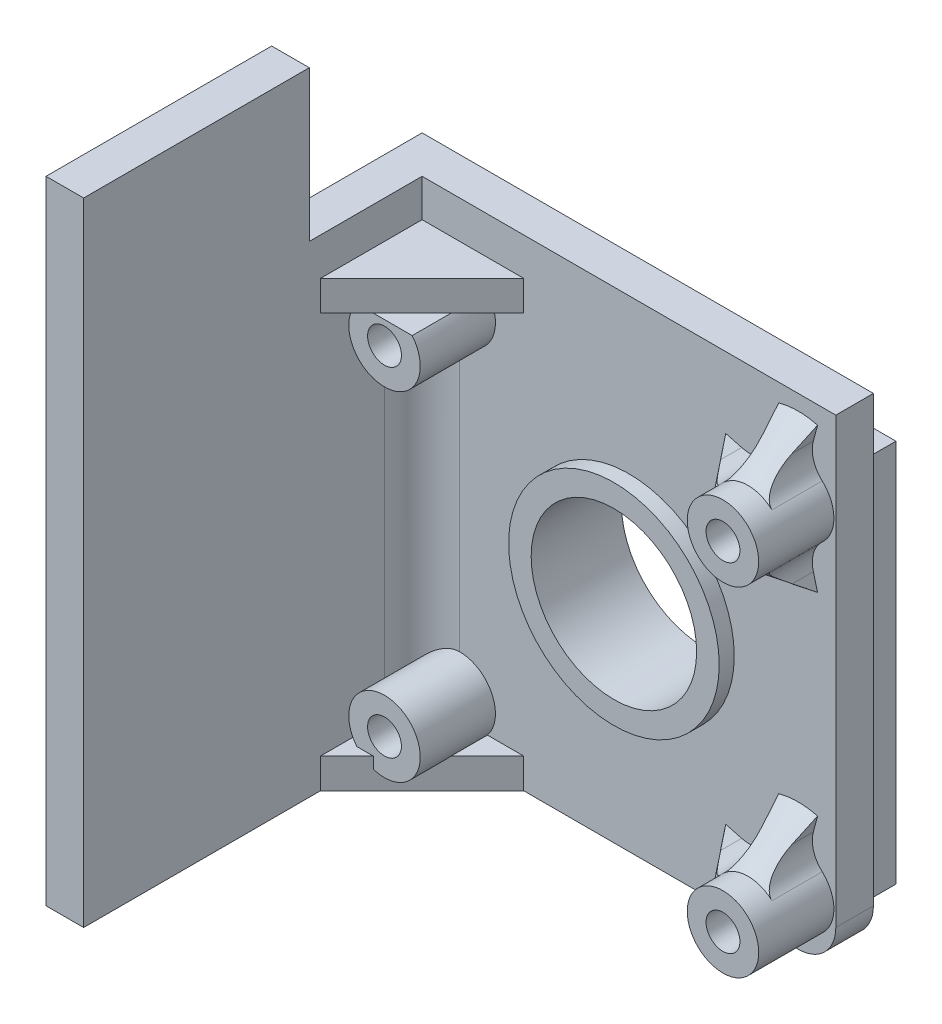
SolidWorks part; units mm, degrees
note: '?' marks a value the reader was unsure of.
ref_plane "Front Plane" through (0, 0, 0) normal (0, 0, 1) x (1, 0, 0)
ref_plane "Top Plane" through (0, 0, 0) normal (0, 1, 0) x (1, 0, 0)
ref_plane "Right Plane" through (0, 0, 0) normal (1, 0, 0) x (0, 0, -1)
sketch "Sketch2" plane through (0, 0, 0) normal (0, 0, 1) x (1, 0, 0)
  line L0 (0, 0) -> (45, 45) construction
  line L1 (0, 0) -> (45, 0)
  line L2 (0, 0) -> (0, 45)
  line L3 (0, 45) -> (45, 45)
  line L4 (45, 0) -> (45, 45)
  line L6 (-5, 52) -> (50, 52)
  line L7 (-5, 52) -> (-5, -7)
  line L8 (-5, -7) -> (50, -7)
  line L9 (50, 52) -> (50, -7)
  line L10 (-5, 52) -> (50, -7) construction
  line L11 (-5, -7) -> (50, 52) construction
  circle A0 centre (0, 45) radius 1.6
  circle A1 centre (45, 45) radius 1.6
  circle A2 centre (45, 0) radius 1.6
  circle A3 centre (0, 0) radius 1.6
  circle A4 centre (22.5, 22.5) radius 11
  point P9 (22.5, 22.5)
  dimension "D3" = 3.2
  dimension "D6" = 22
  dimension "D1" = 45
  dimension "D2" = 45
  dimension "D4" = 5
  dimension "D5" = 7
extrude "Boss-Extrude1" add sketch "Sketch2" along normal blind 5 contours L9 L6 L7 L8 A3 L2 A0 L3 A1 L4 A2 L1 | A3 L1 A2 L4 A1 L3 A0 L2
sketch "Sketch4" plane through (0, 0, 0) normal (0, 0, -1) x (-1, 0, 0)
  line L0 (5, 52) -> (-50, 52) construction
  line L1 (5, -7) -> (10, -7)
  line L2 (5, -7) -> (5, 52)
  line L3 (5, 52) -> (10, 52)
  line L4 (10, -7) -> (10, 52)
  dimension "D1" = 5
extrude "Boss-Extrude2" add sketch "Sketch4" against normal blind 50
sketch "Sketch5" plane through (0, 52, 0) normal (0, 1, 0) x (1, 0, 0)
  line L0 (-5, -5) -> (8.5128, -5)
  line L1 (-5, -5) -> (50, -5) construction
  line L2 (8.5128, -5) -> (-5, -18.5128)
  line L3 (-5, -50) -> (-5, -5) construction
  line L4 (-5, -18.5128) -> (-5, -5)
  point P2 (0, 0)
  point P5 (-10, -9.0838)
  point P7 (0, 0)
  point P10 (8.5128, -5)
extrude "Boss-Extrude3" add sketch "Sketch5" against normal blind 4
ref_plane "Plane1" through (0, 22.5, 0) normal (0, 1, 0) x (1, 0, 0)
fillet "Fillet2" radius 5 1 edges at (50, -7, 2.5)
sketch "Sketch7" plane through (0, 52, 0) normal (0, 1, 0) x (1, 0, 0)
  line L0 (-5, -50) -> (-10, -50) construction
  line L1 (-5, -50) -> (-10, -50)
  line L2 (-5, -50) -> (-5, 0)
  line L3 (-5, 0) -> (-10, 0)
  line L4 (-10, -50) -> (-10, 0)
  line L6 (-10, 0) -> (50, 0) construction
  line L7 (-10, -50) -> (-10, 0) construction
  point P12 (0, 0)
extrude "Boss-Extrude4" add sketch "Sketch7" along normal blind 5
sketch "Sketch8" plane through (-10, 0, 0) normal (-1, 0, 0) x (0, 0, 1)
  line L1 (5, 52) -> (0, 52)
  line L2 (5, 52) -> (5, 57)
  line L3 (5, 57) -> (0, 57)
  line L4 (0, 52) -> (0, 57)
extrude "Boss-Extrude5" add sketch "Sketch8" along normal up to surface (60 mm away)
sketch "Sketch10" plane through (0, 0, 5) normal (0, 0, 1) x (1, 0, 0)
  line L6 (-5, 48) -> (-5, -7)
  line L7 (-5, 48) -> (-5, -7)
  line L8 (-5, -7) -> (45, -7)
  line L9 (50, -2) -> (50, 57)
  line L10 (50, 57) -> (-5, 57)
  line L11 (-5, 57) -> (-5, 52)
  line L12 (-5, 52) -> (8.5128, 52)
  line L15 (8.5128, 52) -> (8.5128, 48)
  line L16 (-5, -7) -> (45, -7)
  line L17 (50, -2) -> (50, 57)
  line L18 (50, 57) -> (-5, 57)
  line L20 (-5, 52) -> (8.5128, 52)
  line L24 (8.5128, 52) -> (8.5128, 48)
  line L25 (8.5128, 48) -> (-5, 48)
  line L26 (8.5128, 48) -> (-5, 48)
  line L27 (-5, 57) -> (-5, 52)
  circle A0 centre (0, 45) radius 4.75
  arc A1 (45, -7) -> (50, -2) centre (45, -2) ccw
  arc A2 (45, -7) -> (50, -2) centre (45, -2) ccw
  circle A3 centre (45, 45) radius 4.75
  circle A4 centre (45, 0) radius 4.75
  circle A5 centre (0, 0) radius 4.75
  circle A6 centre (45, 45) radius 2.25
  circle A7 centre (0, 45) radius 2.25
  circle A8 centre (0, 0) radius 2.25
  circle A9 centre (45, 0) radius 2.25
  dimension "D2" = 9.5
  dimension "D3" = 4.5
  dimension "D1" = 0
extrude "Boss-Extrude6" add sketch "Sketch10" along normal blind 10
ref_axis "Axis1" through (45, 45, 15) along (0, 0, -1)
ref_plane "Plane2" through (40.25, 0, 0) normal (-1, 0, 0) x (0, 0, 1)
ref_plane "Plane3" through (0, 45, 0) normal (0, 1, 0) x (0, 0, -1)
sketch "Sketch11" plane through (0, 45, 0) normal (0, 1, 0) x (0, 0, -1)
  line L0 (-5, -40.25) -> (-5, -35.0322)
  line L1 (-5, -35.0322) -> (-11.6774, -40.25)
  line L2 (-5, -40.25) -> (-15, -40.25) construction
  line L3 (-11.6774, -40.25) -> (-5, -40.25)
revolve "Revolve1" add sketch "Sketch11" angle 30 mid plane about axis through (45, 45, 15) along (0, 0, -1)
pattern_circular "CirPattern1" count 2 every 270 about axis through (45, 45, 15) along (0, 0, -1) of "Revolve1"
ref_axis "Axis2" through (45, 0, 15) along (0, 0, -1)?
mirror "Mirror1" about plane through (0, 22.5, 0) normal (0, 1, 0) of "Revolve1", "CirPattern1"
pattern_circular "CirPattern2" count 2 every 270 about axis through (45, 45, 15) along (0, 0, -1) of "Revolve1"
sketch "Sketch12" plane through (0, 0, 5) normal (0, 0, 1) x (1, 0, 0)
  circle A0 centre (22.5, 22.5) radius 14
  circle A1 centre (22.5, 22.5) radius 11 construction
  circle A2 centre (22.5, 22.5) radius 11
  dimension "D1" = 3
extrude "Boss-Extrude7" add sketch "Sketch12" along normal blind 2
mirror "Mirror2" about plane through (0, 22.5, 0) normal (0, 1, 0) of "Boss-Extrude3"
fillet "Fillet3" radius 4 10 edges at (46.2294, 40.4119, 8.3387) (46.2294, 49.5881, 8.3387) (43.7706, 49.5881, 8.3387) (40.4119, 46.2294, 8.3387) (43.7706, 40.4119, 8.3387) (40.4119, 43.7706, 8.3387) (40.4119, -1.2294, 8.3387) (40.4119, 1.2294, 8.3387) (43.7706, 4.5881, 8.3387) (46.2294, 4.5881, 8.3387)
sketch "Sketch14" plane through (0, 57, 0) normal (0, 1, 0) x (1, 0, 0)
  line L0 (50, 0) -> (-10, 0) construction
  line L1 (-10, -50) -> (-5, -50)
  line L2 (-10, -50) -> (-10, -20)
  line L3 (-10, -20) -> (-5, -20)
  line L4 (-5, -50) -> (-5, -20)
  dimension "D1" = 20
extrude "Boss-Extrude8" add sketch "Sketch14" along normal blind 20
fillet "Fillet4" radius 5 1 edges at (-5, 22.5, 5)
sketch "Sketch15" plane through (0, 0, 0) normal (0, 0, -1) x (-1, 0, 0)
  line L0 (-48, -3) -> (-48, 48)
  line L1 (-45, 0) -> (0, 0)
  line L2 (-45, 0) -> (-45, 45)
  line L3 (-45, 45) -> (0, 45)
  line L4 (0, 0) -> (0, 45)
  line L5 (-48, 48) -> (3, 48)
  line L6 (3, -3) -> (3, 48)
  line L7 (-48, -3) -> (3, -3)
  circle A0 centre (-45, 0) radius 1.6 construction
  circle A1 centre (0, 0) radius 1.6 construction
  circle A2 centre (0, 45) radius 1.6 construction
  circle A3 centre (-45, 45) radius 1.6 construction
  circle A4 centre (-45, 0) radius 1.6
  circle A5 centre (0, 0) radius 1.6
  circle A6 centre (0, 45) radius 1.6
  circle A7 centre (-45, 45) radius 1.6
  circle M9 centre (0, 45) radius 1.6
  circle M10 centre (-45, 45) radius 1.6
  circle M11 centre (0, 0) radius 1.6
  circle M12 centre (-45, 0) radius 1.6
  circle M18 centre (-22.5, 22.5) radius 11
  dimension "D1" = 3
extrude "Boss-Extrude9" add sketch "Sketch15" along normal blind 5 contours L4 L3 L2 L1 M11 M9 M10 M12 M18 | L0 L7 L6 L5 L4 L1 L2 L3 M11 M12 M10 M9
